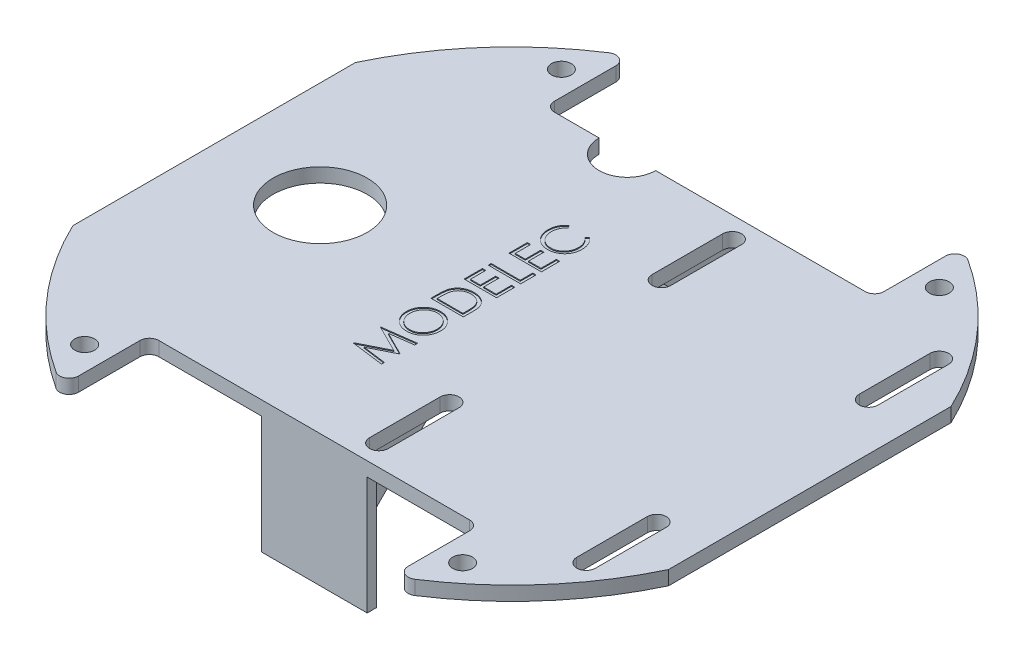
SolidWorks part; units mm, degrees
ref_plane "Plan de face" through (0, 0, 0) normal (0, 0, 1) x (1, 0, 0)
ref_plane "Plan de dessus" through (0, 0, 0) normal (0, 1, 0) x (1, 0, 0)
ref_plane "Plan de droite" through (0, 0, 0) normal (1, 0, 0) x (0, 0, -1)
sketch "Esquisse1" plane through (0, 0, 0) normal (0, 1, 0) x (1, 0, 0)
  line L0 (0, 83.5544) -> (0, -91.5756) construction
  line L1 (-140.3714, 0) -> (145.9862, 0) construction
  line L2 (35, 42) -> (-35, 42)
  line L3 (-35, 42) -> (-35, 60.6218)
  line L4 (-63.2456, -30) -> (-63.2456, 30)
  line L5 (-37, 57.0526) -> (-37, 42) construction
  line L6 (-46.4527, 49.6603) -> (-37, 45.0526) construction
  line L7 (-41.7264, 47.3565) -> (-37, 57.0526) construction
  line L8 (-35, 60.6218) -> (-65.5835, 60.6218) construction
  line L9 (-35, -42) -> (-35, -60.6218)
  line L10 (35, -42) -> (-35, -42)
  line L11 (35, 42) -> (35, 60.6218)
  line L12 (63.2456, -30) -> (63.2456, 30)
  line L13 (35, -42) -> (35, -60.6218)
  line L14 (9.2456, 37.5) -> (9.2456, 22.5) construction
  line L17 (31.2456, 0) -> (31.2456, 33.6619) construction
  line L18 (11.2456, 37.5) -> (11.2456, 22.5)
  line L21 (7.2456, 37.5) -> (7.2456, 22.5)
  line L24 (9.2456, -22.5) -> (9.2456, -37.5) construction
  line L27 (11.2456, -22.5) -> (11.2456, -37.5)
  line L28 (7.2456, -22.5) -> (7.2456, -37.5)
  line L29 (53.2456, -22.5) -> (53.2456, -37.5) construction
  line L30 (51.2456, -22.5) -> (51.2456, -37.5)
  line L31 (55.2456, -22.5) -> (55.2456, -37.5)
  line L32 (53.2456, 37.5) -> (53.2456, 22.5) construction
  line L33 (51.2456, 37.5) -> (51.2456, 22.5)
  line L34 (55.2456, 37.5) -> (55.2456, 22.5)
  circle A0 centre (0, 0) radius 70 construction
  arc A1 (-63.2456, 30) -> (-35, 60.6218) centre (0, 0) cw
  circle A2 centre (0, 0) radius 68 construction
  arc A3 (-46.4527, 49.6603) -> (-37, 45.0526) centre (-37, 57.0526) ccw construction
  circle A4 centre (-40.1347, 50.6218) radius 2.1
  circle A5 centre (-40.1347, -50.6218) radius 2.1
  arc A6 (-63.2456, -30) -> (-35, -60.6218) centre (0, 0) ccw
  circle A7 centre (40.1347, 50.6218) radius 2.1
  arc A8 (63.2456, 30) -> (35, 60.6218) centre (0, 0) ccw
  circle A9 centre (40.1347, -50.6218) radius 2.1
  arc A10 (63.2456, -30) -> (35, -60.6218) centre (0, 0) cw
  circle A11 centre (-40.7456, 0) radius 10
  arc A20 (11.2456, 37.5) -> (7.2456, 37.5) centre (9.2456, 37.5) ccw
  arc A21 (7.2456, 22.5) -> (11.2456, 22.5) centre (9.2456, 22.5) ccw
  arc A22 (11.2456, -22.5) -> (7.2456, -22.5) centre (9.2456, -22.5) ccw
  arc A23 (7.2456, -37.5) -> (11.2456, -37.5) centre (9.2456, -37.5) ccw
  arc A24 (51.2456, -22.5) -> (55.2456, -22.5) centre (53.2456, -22.5) cw
  arc A25 (55.2456, -37.5) -> (51.2456, -37.5) centre (53.2456, -37.5) cw
  arc A26 (51.2456, 37.5) -> (55.2456, 37.5) centre (53.2456, 37.5) cw
  arc A27 (55.2456, 22.5) -> (51.2456, 22.5) centre (53.2456, 22.5) cw
  arc A28 (-23.5, 42) -> (-11.5, 42) centre (-17.5, 42) ccw
  point P28 (-63.2456, 0)
  point P34 (0, 42)
  point P39 (0, -42)
  point P41 (9.2456, 30)
  point P49 (9.2456, -30)
  point P57 (53.2456, -30)
  point P64 (53.2456, 30)
  dimension "D1" = 140
  dimension "D2" = 42
  dimension "D5" = 136
  dimension "D7" = 12
  dimension "D8" = 4.2
  dimension "D10" = 20
  dimension "D17" = 6
  dimension "D3" = 35
  dimension "D4" = 30
  dimension "D6" = 2
  dimension "D9" = 10
  dimension "D11" = 22.5
  dimension "D12" = 15
  dimension "D13" = 60
  dimension "D14" = 44
  dimension "D15" = 4
  dimension "D16" = 10
  dimension "D18" = 17.5
extrude "Boss.-Extru.1" add sketch "Esquisse1" along normal blind 3 contours A28 L2 L3 A1 L4 A6 L9 L10 L13 A10 L12 A8 L11 A23 L28 A22 L27 A21 L21 A20 L18 A11 A9 A5 A4 A7 L31 A25 L30 A24 L34 A27 L33 A26 region at (0.4438, 0, 0.2097)
fillet "Congé1" radius 2 8 edges at (35, 1.5, -42) (35, 1.5, -60.6218) (-35, 1.5, -60.6218) (-35, 1.5, -42) (35, 1.5, 42) (35, 1.5, 60.6218) (-35, 1.5, 42) (-35, 1.5, 60.6218)
sketch "Esquisse5" plane through (0, 0, 0) normal (0, -1, 0) x (1, 0, 0)
  line L0 (-72.6895, 0) -> (107.3438, 0) construction
  line L1 (11.25, 42) -> (11.25, 40)
  line L2 (11.25, 40) -> (-11.25, 40)
  line L3 (-11.25, 40) -> (-11.25, 42)
  line L4 (0, 57.0526) -> (0, -69.7312) construction
  line L5 (11.25, -42) -> (11.25, -40)
  line L6 (11.25, -40) -> (-11.25, -40)
  line L7 (-11.25, -40) -> (-11.25, -42)
  line L9 (35, -44) -> (35, -57.0526)
  line L10 (63.2456, -30) -> (63.2456, 30)
  line L11 (35, 57.0526) -> (35, 44)
  line L12 (33, 42) -> (-33, 42)
  line L13 (-35, 44) -> (-35, 57.0526)
  line L14 (-63.2456, 30) -> (-63.2456, -30)
  line L15 (-35, -57.0526) -> (-35, -44)
  line L16 (-33, -42) -> (-23.5, -42)
  line L17 (-11.5, -42) -> (33, -42)
  line L18 (35, -44) -> (35, -57.0526)
  line L19 (63.2456, -30) -> (63.2456, 30)
  line L20 (35, 57.0526) -> (35, 44)
  line L21 (33, 42) -> (-33, 42)
  line L22 (-35, 44) -> (-35, 57.0526)
  line L23 (-63.2456, 30) -> (-63.2456, -30)
  line L24 (-35, -57.0526) -> (-35, -44)
  line L25 (-33, -42) -> (-23.5, -42)
  line L26 (-11.5, -42) -> (33, -42)
  arc A13 (35, -57.0526) -> (38.0882, -58.7306) centre (37, -57.0526) ccw
  arc A14 (38.0882, -58.7306) -> (63.2456, -30) centre (0, 0) ccw
  arc A15 (63.2456, 30) -> (38.0882, 58.7306) centre (0, 0) ccw
  arc A16 (38.0882, 58.7306) -> (35, 57.0526) centre (37, 57.0526) ccw
  arc A17 (33, 42) -> (35, 44) centre (33, 44) ccw
  arc A18 (-35, 44) -> (-33, 42) centre (-33, 44) ccw
  arc A19 (-35, 57.0526) -> (-38.0882, 58.7306) centre (-37, 57.0526) ccw
  arc A20 (-38.0882, 58.7306) -> (-63.2456, 30) centre (0, 0) ccw
  arc A21 (-63.2456, -30) -> (-38.0882, -58.7306) centre (0, 0) ccw
  arc A22 (-38.0882, -58.7306) -> (-35, -57.0526) centre (-37, -57.0526) ccw
  arc A23 (-33, -42) -> (-35, -44) centre (-33, -44) ccw
  arc A24 (-11.5, -42) -> (-23.5, -42) centre (-17.5, -42) ccw
  arc A25 (35, -44) -> (33, -42) centre (33, -44) ccw
  arc A26 (35, -57.0526) -> (38.0882, -58.7306) centre (37, -57.0526) ccw
  arc A27 (38.0882, -58.7306) -> (63.2456, -30) centre (0, 0) ccw
  arc A28 (63.2456, 30) -> (38.0882, 58.7306) centre (0, 0) ccw
  arc A29 (38.0882, 58.7306) -> (35, 57.0526) centre (37, 57.0526) ccw
  arc A30 (33, 42) -> (35, 44) centre (33, 44) ccw
  arc A31 (-35, 44) -> (-33, 42) centre (-33, 44) ccw
  arc A32 (-35, 57.0526) -> (-38.0882, 58.7306) centre (-37, 57.0526) ccw
  arc A33 (-38.0882, 58.7306) -> (-63.2456, 30) centre (0, 0) ccw
  arc A34 (-63.2456, -30) -> (-38.0882, -58.7306) centre (0, 0) ccw
  arc A35 (-38.0882, -58.7306) -> (-35, -57.0526) centre (-37, -57.0526) ccw
  arc A36 (-33, -42) -> (-35, -44) centre (-33, -44) ccw
  arc A37 (-11.5, -42) -> (-23.5, -42) centre (-17.5, -42) ccw
  arc A38 (35, -44) -> (33, -42) centre (33, -44) ccw
  line M36 (33, 42) -> (-33, 42)
  line M48 (-11.5, -42) -> (33, -42)
  dimension "D2" = 2
  dimension "D3" = 22.5
  dimension "D1" = 0
extrude "Boss.-Extru.2" add sketch "Esquisse5" along normal blind 25 contours L3 L2 L1 M36 | L6 L7 L5 M48 region at (0, 0, 41) region at (0, 0, -41)
sketch "Esquisse6" plane through (0, 0, 40) normal (0, 0, -1) x (-1, 0, 0)
  line L0 (-7, 0) -> (-7, -15)
  line L1 (-7, -15) -> (-4, -15)
  line L2 (-4, -15) -> (-4, 0)
  line L3 (0, 8.5664) -> (0, -28.8137) construction
  line L4 (11.25, 0) -> (-11.25, 0)
  line L5 (-11.25, 0) -> (-11.25, -25)
  line L6 (-11.25, -25) -> (11.25, -25)
  line L7 (11.25, -25) -> (11.25, 0)
  line L8 (11.25, 0) -> (-11.25, 0)
  line L9 (-11.25, 0) -> (-11.25, -25)
  line L10 (-11.25, -25) -> (11.25, -25)
  line L11 (11.25, -25) -> (11.25, 0)
  line L12 (4, -15) -> (4, 0)
  line L13 (7, -15) -> (4, -15)
  line L14 (7, 0) -> (7, -15)
  line M9 (11.25, 0) -> (-11.25, 0)
  dimension "D2" = 3
  dimension "D3" = 15
  dimension "D4" = 4
  dimension "D1" = 0
extrude "Boss.-Extru.3" add sketch "Esquisse6" along normal blind 15 contours L14 L8 L12 L13 | L1 L2 L0 M9 region at (5.5, -7.5, 40) region at (-5.5, -7.5, 40)
chamfer "Chanfrein1" distance 15 angle 45 2 edges at (-5.5, -15, 25) (5.5, -15, 25)
mirror "Symétrie3" about plane through (0, 0, 0) normal (0, 0, 1) of "Chanfrein1", "Boss.-Extru.3"
sketch "Esquisse7" plane through (0, 3, 0) normal (0, 1, 0) x (1, 0, 0)
  line L0 (-5, 42) -> (-5, -42) construction
  line L1 (33, 42) -> (-11.5, 42) construction
  line L2 (33, -42) -> (-33, -42) construction
  text T0 "MODELEC" font "Century Gothic" height in points 26
  dimension "D1" = 5
extrude "Enlèv. mat.-Extru.2" cut sketch "Esquisse7" against normal blind 0.2
